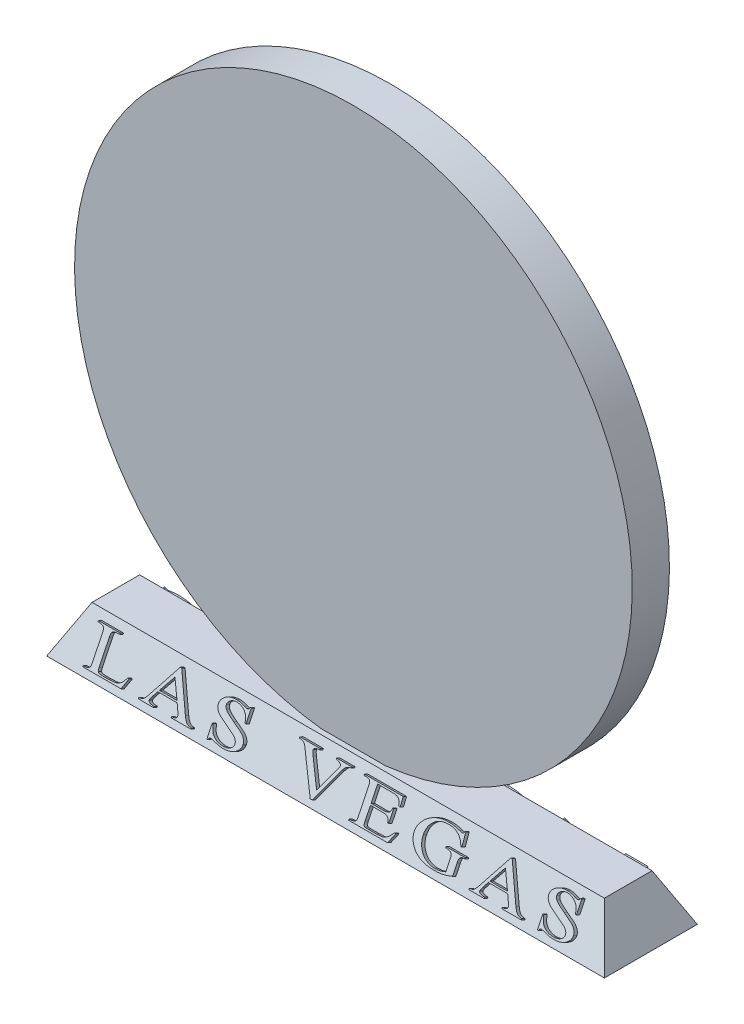
SolidWorks part; units mm, degrees
ref_plane "Front Plane" through (0, 0, 0) normal (0, 0, 1) x (1, 0, 0)
ref_plane "Top Plane" through (0, 0, 0) normal (0, 1, 0) x (1, 0, 0)
ref_plane "Right Plane" through (0, 0, 0) normal (1, 0, 0) x (0, 0, -1)
sketch "Sketch1" plane through (0, 0, 0) normal (0, 1, 0) x (1, 0, 0)
  line L1 (38.1, -6.35) -> (-38.1, -6.35)
  line L2 (38.1, -6.35) -> (38.1, 6.35)
  line L3 (38.1, 6.35) -> (-38.1, 6.35)
  line L4 (-38.1, -6.35) -> (-38.1, 6.35)
  line L5 (38.1, -6.35) -> (-38.1, 6.35) construction
  line L6 (38.1, 6.35) -> (-38.1, -6.35) construction
  point P0 (0, 0)
extrude "Boss-Extrude1" add sketch "Sketch1" along normal blind 6.35 draft 26
sketch "Sketch2" plane through (0, 0, 0) normal (0, 0, 1) x (1, 0, 0)
  circle A0 centre (0, 44.196) radius 38.1
extrude "Boss-Extrude2" add sketch "Sketch2" along normal blind 2.54 and the other way blind 2.54
sketch "Sketch5" plane through (0, 2.5019, 5.1297) normal (0, 0.4384, 0.8988) x (1, 0, 0)
  text T0 "LAS VEGAS" font "Times New Roman" height in points 20
sketch "Sketch6" plane through (0, 2.5019, -5.1297) normal (0, 0.4384, -0.8988) x (-1, 0, 0)
  text T0 "LAS VEGAS" font "Times New Roman" height in points 20
extrude "Boss-Extrude3" add sketch "Sketch5" along normal blind 0.508
extrude "Boss-Extrude4" add sketch "Sketch6" along normal blind 0.508
